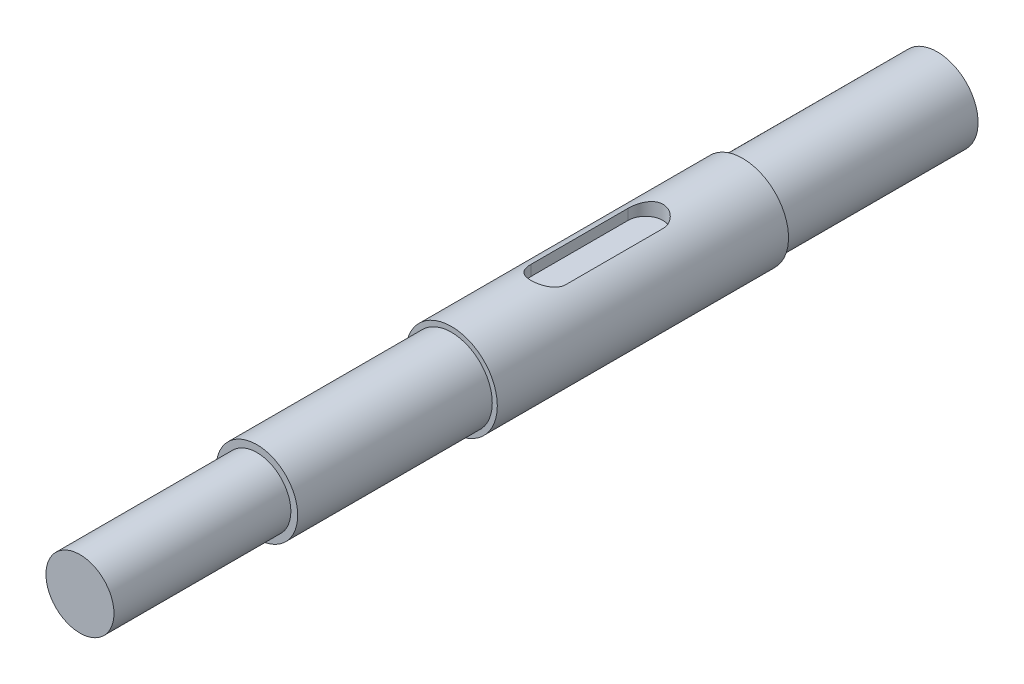
SolidWorks part; units mm, degrees
ref_plane "前视基准面" through (0, 0, 0) normal (0, 0, 1) x (1, 0, 0)
ref_plane "上视基准面" through (0, 0, 0) normal (0, 1, 0) x (1, 0, 0)
ref_plane "右视基准面" through (0, 0, 0) normal (1, 0, 0) x (0, 0, -1)
sketch "草图1" plane through (0, 0, 0) normal (0, 0, 1) x (1, 0, 0)
  circle A0 centre (0, 0) radius 3.37
extrude "凸台-拉伸1" add sketch "草图1" along normal mid plane 50 from surface
sketch "草图2" plane through (0, 0, 0) normal (0, 0, 1) x (1, 0, 0)
  line L0 (-1.2867, 4.34) -> (1.2867, 4.34)
  line L1 (-1.2867, 4.34) -> (-1.2867, 3.1147)
  line L2 (1.2867, 4.34) -> (1.2867, 3.1147)
  circle A1 centre (0, 0) radius 3.37 construction
  circle A3 centre (0, 0) radius 3.37
  arc A4 (-1.2867, 3.1147) -> (1.2867, 3.1147) centre (0, 0) ccw
  point P2 (0, 4.34)
  dimension "D1" = 4.34
  dimension "D2" = 0
extrude "凸台-拉伸2" add sketch "草图2" against normal up to surface (7.1235 mm away) from surface
sketch "草图3" plane through (0, 0, 49.7611) normal (0, 0, 1) x (1, 0, 0)
  circle A1 centre (0, 0) radius 3.37
  circle A2 centre (0, 0) radius 3.37
  dimension "D1" = 0
extrude "凸台-拉伸3" add sketch "草图3" along normal blind 13
sketch "草图4" plane through (0, 0, 62.7611) normal (0, 0, 1) x (1, 0, 0)
  circle A0 centre (0, 0) radius 2.5
  circle A1 centre (0, 0) radius 3.37
  dimension "D1" = 5
extrude "切除-拉伸1" cut sketch "草图4" against normal blind 13
sketch "草图5" plane through (0, 0, 49.7611) normal (0, 0, 1) x (1, 0, 0)
  circle A0 centre (0, 0) radius 3.37
  circle A2 centre (0, 0) radius 3
  dimension "D1" = 6
extrude "切除-拉伸2" cut sketch "草图5" against normal blind 14.3
sketch "草图6" plane through (0, 0, -0.2389) normal (0, 0, -1) x (-1, 0, 0)
  circle A0 centre (0, 0) radius 3.37
  circle A1 centre (0, 0) radius 3
  dimension "D1" = 6
extrude "切除-拉伸3" cut sketch "草图6" against normal blind 14.3
sketch "草图7" plane through (0, 4.34, 0) normal (0, 1, 0) x (1, 0, 0)
  line L0 (0, -28.3229) -> (0, -21.1994) construction
  line L1 (-1.2867, -28.3229) -> (1.2867, -28.3229) construction
  line L2 (-1.2867, -21.1994) -> (1.2867, -21.1994) construction
  line L3 (-1.2867, -28.3229) -> (-1.2867, -21.1994)
  line L4 (1.2867, -28.3229) -> (1.2867, -21.1994)
  line L5 (-1.2867, -21.1994) -> (-1.2867, -28.3229) construction
  arc A0 (-1.2867, -28.3229) -> (1.2867, -28.3229) centre (0, -28.3229) ccw
  arc A1 (1.2867, -21.1994) -> (-1.2867, -21.1994) centre (0, -21.1994) ccw
  point P6 (0, -24.7611)
extrude "切除-拉伸4" cut sketch "草图7" against normal blind 2
